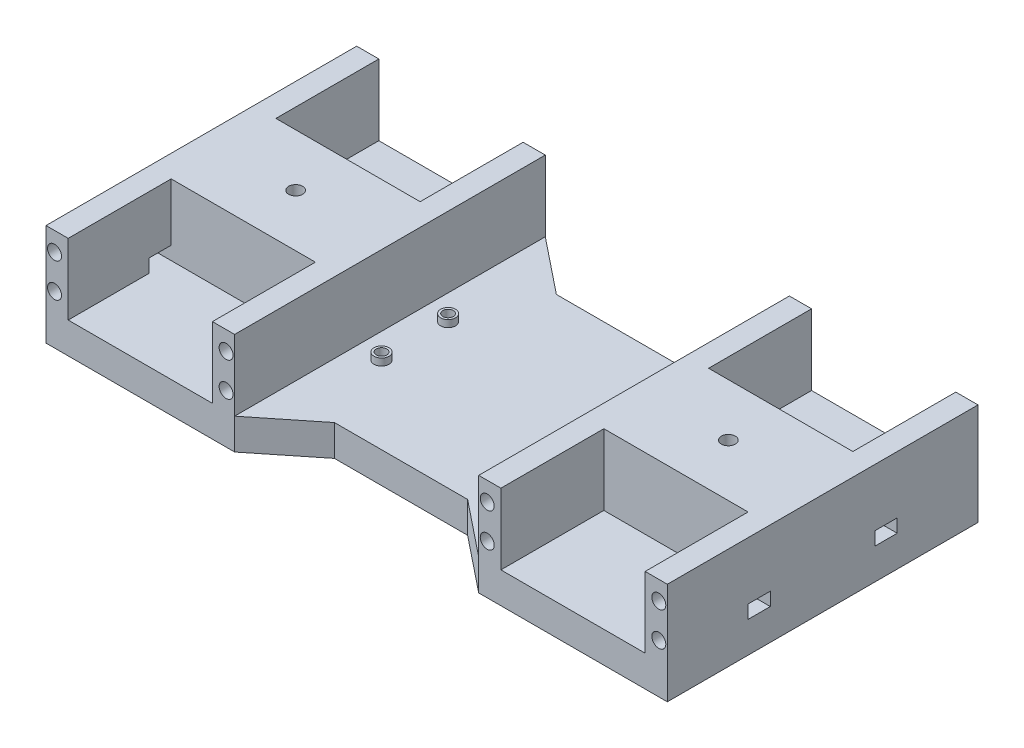
SolidWorks part; units mm, degrees
ref_plane "Front Plane" through (0, 0, 0) normal (0, 0, 1) x (1, 0, 0)
ref_plane "Top Plane" through (0, 0, 0) normal (0, 1, 0) x (1, 0, 0)
ref_plane "Right Plane" through (0, 0, 0) normal (1, 0, 0) x (0, 0, -1)
sketch "Sketch2" plane through (0, 0, 0) normal (0, 1, 0) x (1, 0, 0)
  line L0 (88.9, 0) -> (88.9, 88.9) construction
  line L1 (0, 0) -> (177.8, 0)
  line L2 (0, 0) -> (0, 88.9)
  line L3 (0, 88.9) -> (177.8, 88.9)
  line L4 (177.8, 0) -> (177.8, 88.9)
  line L5 (44.45, 12.7) -> (133.35, 12.7) construction
  line L6 (44.45, 12.7) -> (44.45, 76.2) construction
  line L7 (44.45, 76.2) -> (133.35, 76.2) construction
  line L8 (133.35, 12.7) -> (133.35, 76.2) construction
  line L9 (171.45, 0) -> (130.175, 0)
  line L10 (171.45, 0) -> (171.45, 29.464)
  line L11 (171.45, 29.464) -> (130.175, 29.464)
  line L12 (130.175, 0) -> (130.175, 29.464)
  line L17 (69.85, 12.7) -> (53.975, 12.7)
  line L18 (107.95, 12.7) -> (123.825, 12.7)
  line L19 (0, 44.45) -> (177.8, 44.45) construction
  line L24 (6.35, 29.464) -> (47.625, 29.464)
  line L25 (47.625, 0) -> (47.625, 29.464)
  line L26 (6.35, 0) -> (47.625, 0)
  line L27 (6.35, 0) -> (6.35, 29.464)
  line L28 (171.45, 59.436) -> (130.175, 59.436)
  line L29 (130.175, 88.9) -> (130.175, 59.436)
  line L30 (171.45, 88.9) -> (130.175, 88.9)
  line L31 (171.45, 88.9) -> (171.45, 59.436)
  line L36 (6.35, 88.9) -> (6.35, 59.436)
  line L37 (6.35, 88.9) -> (47.625, 88.9)
  line L38 (47.625, 88.9) -> (47.625, 59.436)
  line L39 (6.35, 59.436) -> (47.625, 59.436)
  line L44 (53.975, 0) -> (69.85, 12.7)
  line L45 (69.85, 12.7) -> (107.95, 12.7)
  line L46 (107.95, 12.7) -> (123.825, 0)
  line L47 (53.975, 88.9) -> (69.85, 76.2)
  line L48 (69.85, 76.2) -> (107.95, 76.2)
  line L49 (107.95, 76.2) -> (123.825, 88.9)
  line L50 (107.95, 76.2) -> (123.825, 76.2)
  line L51 (0, 88.9) -> (53.975, 88.9)
  line L52 (0, 88.9) -> (0, 0)
  line L53 (0, 0) -> (53.975, 0)
  line L54 (53.975, 88.9) -> (53.975, 0)
  line L55 (177.8, 0) -> (123.825, 0)
  line L56 (177.8, 0) -> (177.8, 88.9)
  line L57 (177.8, 88.9) -> (123.825, 88.9)
  line L58 (123.825, 0) -> (123.825, 88.9)
  line L59 (69.85, 76.2) -> (53.975, 76.2)
  point P9 (448.483, -253.2129)
  dimension "D1" = 88.9
  dimension "D2" = 177.8
  dimension "D3" = 63.5
  dimension "D4" = 88.9
  dimension "D5" = 31.75
  dimension "D6" = 41.275
  dimension ".9448" = 29.464
  dimension "D7" = 6.35
  dimension "D8" = 6.35
  dimension "D9" = 44.45
  dimension "D10" = 38.1
  dimension "D11" = 6.35
extrude "Boss-Extrude1" add sketch "Sketch2" along normal blind 8.89 contours L36 L39 L38 L3 | L27 L1 L25 L24 | L54 L3 L38 L39 L36 L2 L1 L27 L24 L25 | L48 L59 L54 L17 L45 L18 L58 L50 | L17 L54 L44 | L46 L58 L18 | L58 L1 L12 L11 L10 L4 L3 L31 L28 L29 | L12 L1 L10 L11 | L31 L3 L29 L28 | L50 L58 L49 | L59 L47 L54 region at (26.9875, 0, -44.45) region at (26.9875, 0, -14.732) region at (26.9875, 0, -74.168) region at (59.2667, 0, -8.4667) region at (150.8125, 0, -44.45) region at (118.5333, 0, -8.4667) region at (88.9, 0, -44.45) region at (59.2667, 0, -80.4333) region at (150.8125, 0, -14.732) region at (118.5333, 0, -80.4333) region at (150.8125, 0, -74.168)
extrude "Boss-Extrude2" add sketch "Sketch2<3>" along normal blind 29.144 contours L54 L3 L38 L39 L36 L2 L1 L27 L24 L25 | L58 L1 L12 L11 L10 L4 L3 L31 L28 L29 region at (26.9875, 0, -44.45) region at (150.8125, 0, -44.45)
sketch "Sketch2<3>" plane through (0, 0, 0) normal (0, 1, 0) x (1, 0, 0) same geometry as "Sketch2"
sketch "Sketch6" plane through (0, 29.144, 0) normal (0, 1, 0) x (1, 0, 0)
  line L0 (26.9875, 29.464) -> (26.9875, 44.45) construction
  line L1 (6.35, 29.464) -> (47.625, 29.464) construction
  line L2 (88.9, 0) -> (88.9, 88.9) construction
  line L3 (88.9, 12.7) -> (88.9, 27.7271) construction
  line L4 (69.85, 12.7) -> (107.95, 12.7) construction
  line L5 (88.9, 44.45) -> (106.0706, 44.45) construction
  line L6 (0, 44.45) -> (177.8, 44.45) construction
  circle A0 centre (26.9875, 44.45) radius 2
  circle A1 centre (150.8125, 44.45) radius 2
  dimension "D1" = 4
extrude "Cut-Extrude1" cut sketch "Sketch6" against normal blind 6.5
sketch "Sketch7" plane through (0, 0, 0) normal (0, 0, 1) x (1, 0, 0)
  line L0 (88.9, 0) -> (88.9, 26.7038) construction
  line L1 (2.4375, 14.04) -> (51.5375, 14.04) construction
  line L2 (26.9875, 14.04) -> (26.9875, 8.89) construction
  line L3 (6.35, 8.89) -> (47.625, 8.89) construction
  line L4 (47.625, 8.89) -> (6.35, 8.89) construction
  line L5 (69.85, 0) -> (107.95, 0) construction
  line L6 (150.8125, 14.04) -> (150.8125, 8.89) construction
  line L7 (175.3625, 14.04) -> (126.2625, 14.04) construction
  circle A0 centre (2.4375, 14.04) radius 2
  circle A1 centre (51.5375, 14.04) radius 2
  circle A2 centre (2.4375, 23.74) radius 2
  circle A3 centre (51.5375, 23.74) radius 2
  circle A4 centre (126.2625, 23.74) radius 2
  circle A5 centre (175.3625, 23.74) radius 2
  circle A6 centre (126.2625, 14.04) radius 2
  circle A7 centre (175.3625, 14.04) radius 2
  dimension "D1" = 49.1
  dimension "D2" = 4
  dimension "D3" = 5.15
  dimension "D4" = 9.7
extrude "Cut-Extrude2" cut sketch "Sketch7" against normal blind 6
sketch "Sketch8" plane through (0, 8.89, 0) normal (0, 1, 0) x (1, 0, 0)
  line L0 (88.9, 0) -> (88.9, 88.9) construction
  line L1 (116.713, 53.975) -> (61.087, 53.975) construction
  line L2 (116.713, 53.975) -> (116.713, 34.925) construction
  line L3 (116.713, 34.925) -> (61.087, 34.925) construction
  line L4 (61.087, 53.975) -> (61.087, 34.925) construction
  line L5 (116.713, 53.975) -> (61.087, 34.925) construction
  line L6 (116.713, 34.925) -> (61.087, 53.975) construction
  circle A0 centre (61.087, 53.975) radius 1.5
  circle A1 centre (61.087, 34.925) radius 1.5
  circle A2 centre (116.713, 34.925) radius 1.5
  circle A3 centre (116.713, 53.975) radius 1.5
  point P0 (88.9, 44.45)
  dimension "D3" = 3
  dimension "D1" = 19.05
  dimension "D2" = 55.626
extrude "Extrude-Thin1" add sketch "Sketch8" along normal blind 2 thin contours A1 | A0 | A3 | A2 thin type one direction wall 0.635
extrude "Cut-Extrude3" cut sketch "Sketch8<3>" against normal blind 21.78 contours A0 | A1 | A2 | A3 region at (61.087, 8.89, -53.975) region at (61.087, 8.89, -34.925) region at (116.713, 8.89, -34.925) region at (116.713, 8.89, -53.975)
sketch "Sketch8<3>" plane through (0, 8.89, 0) normal (0, 1, 0) x (1, 0, 0) same geometry as "Sketch8"
extrude "Cut-Extrude4" cut sketch "Sketch7<2>" along normal blind 6 from surface starting at face at (29.9861, 15.9162, -88.9)
sketch "Sketch7<2>" plane through (0, 0, 0) normal (0, 0, 1) x (1, 0, 0) same geometry as "Sketch7"
sketch "Sketch9" plane through (0, 0, 0) normal (-1, 0, 0) x (0, 0, 1)
  line L0 (-29.464, 29.144) -> (-29.464, 8.89) construction
  line L1 (-29.464, 8.89) -> (-23.114, 8.89)
  line L2 (-29.464, 8.89) -> (-29.464, 12.7)
  line L3 (-29.464, 12.7) -> (-23.114, 12.7)
  line L4 (-23.114, 8.89) -> (-23.114, 12.7)
  line L5 (-59.436, 8.89) -> (-65.786, 8.89)
  line L6 (-59.436, 8.89) -> (-59.436, 12.7)
  line L7 (-59.436, 12.7) -> (-65.786, 12.7)
  line L8 (-65.786, 8.89) -> (-65.786, 12.7)
  line L9 (-59.436, 29.144) -> (-59.436, 8.89) construction
  line L10 (-59.436, 8.89) -> (-88.9, 8.89) construction
  point P14 (-64.6241, 14.0781)
  point P15 (-65.5654, 15.0194)
  point P16 (-64.3007, 8.89)
  point P17 (-67.8529, 13.7213)
  point P18 (-67.8664, 12.8265)
  dimension "D1" = 6.35
  dimension "D2" = 3.81
extrude "Cut-Extrude5" cut sketch "Sketch9" against normal blind 6.35
extrude "Cut-Extrude6" cut sketch "Sketch9<2>" along normal blind 6.35 from surface starting at face at (177.8, 14.572, -44.45)
sketch "Sketch9<2>" plane through (0, 0, 0) normal (-1, 0, 0) x (0, 0, 1) same geometry as "Sketch9"
